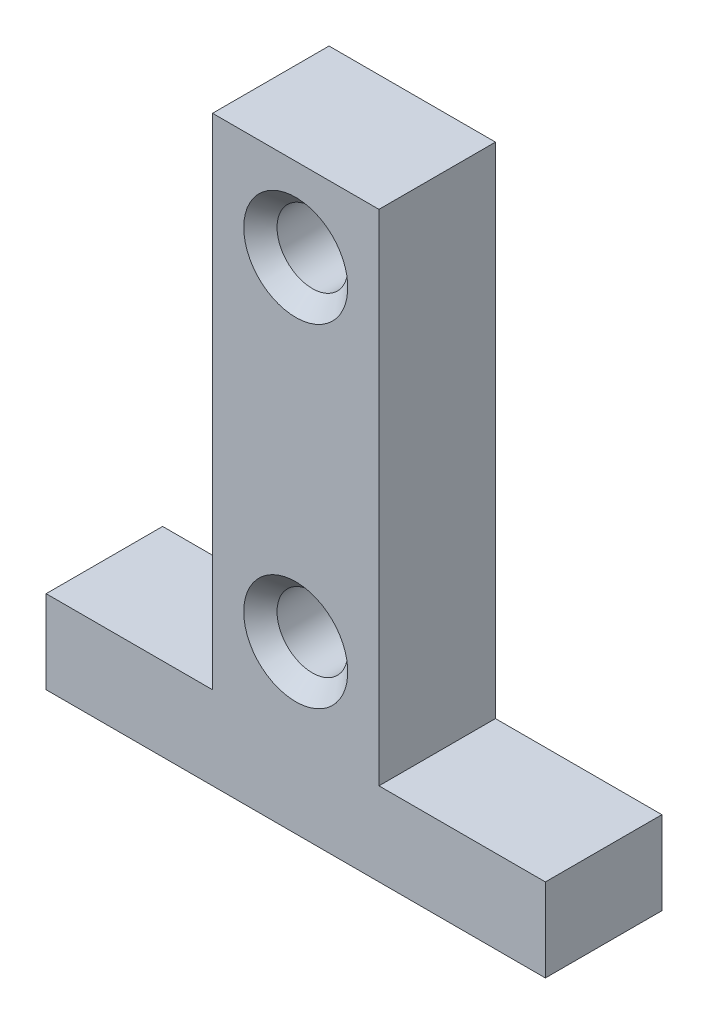
SolidWorks part; units mm, degrees
ref_plane "Front Plane" through (0, 0, 0) normal (0, 0, 1) x (1, 0, 0)
ref_plane "Top Plane" through (0, 0, 0) normal (0, 1, 0) x (1, 0, 0)
ref_plane "Right Plane" through (0, 0, 0) normal (1, 0, 0) x (0, 0, -1)
sketch "Sketch1" plane through (0, 0, 0) normal (0, 0, 1) x (1, 0, 0)
  line L1 (0, 0) -> (10, 0)
  line L2 (0, 0) -> (0, 30)
  line L3 (0, 30) -> (10, 30)
  line L4 (10, 0) -> (10, 30)
  dimension "D1" = 30
  dimension "D2" = 10
extrude "Boss-Extrude1" add sketch "Sketch1" along normal blind 7
sketch "Sketch2" plane through (0, 0, 7) normal (0, 0, 1) x (1, 0, 0)
  line L2 (10, 0) -> (10, 30) construction
  line L4 (0, 0) -> (10, 0) construction
  circle A2 centre (5, 25) radius 2.125
  circle A3 centre (5, 5) radius 2.125
  point P12 (0, 0)
  point P13 (0, 0)
  point P14 (0, 0)
  point P15 (0, 0)
  point P16 (0, 0)
  point P21 (5, 1.5558)
  dimension "D4" = 5
  dimension "D5" = 5
extrude "Cut-Extrude1" cut sketch "Sketch2" against normal blind 7
chamfer "Chamfer1" distance 1 angle 45 2 edges at (7.125, 5, 7) (7.125, 25, 7)
sketch "Sketch3" plane through (0, 0, 0) normal (0, -1, 0) x (1, 0, 0)
  line L0 (0, 7) -> (10, 7) construction
  line L1 (-10, 7) -> (20, 7)
  line L2 (-10, 7) -> (-10, 0)
  line L3 (-10, 0) -> (20, 0)
  line L4 (20, 7) -> (20, 0)
  line L5 (0, 0) -> (10, 0) construction
  point P6 (5, 7)
  point P7 (5, 7)
  point P10 (5, 0)
  point P11 (5, 0)
  point P12 (-9.6782, 3.9095)
  dimension "D1" = 30
extrude "Boss-Extrude2" add sketch "Sketch3" along normal blind 5
